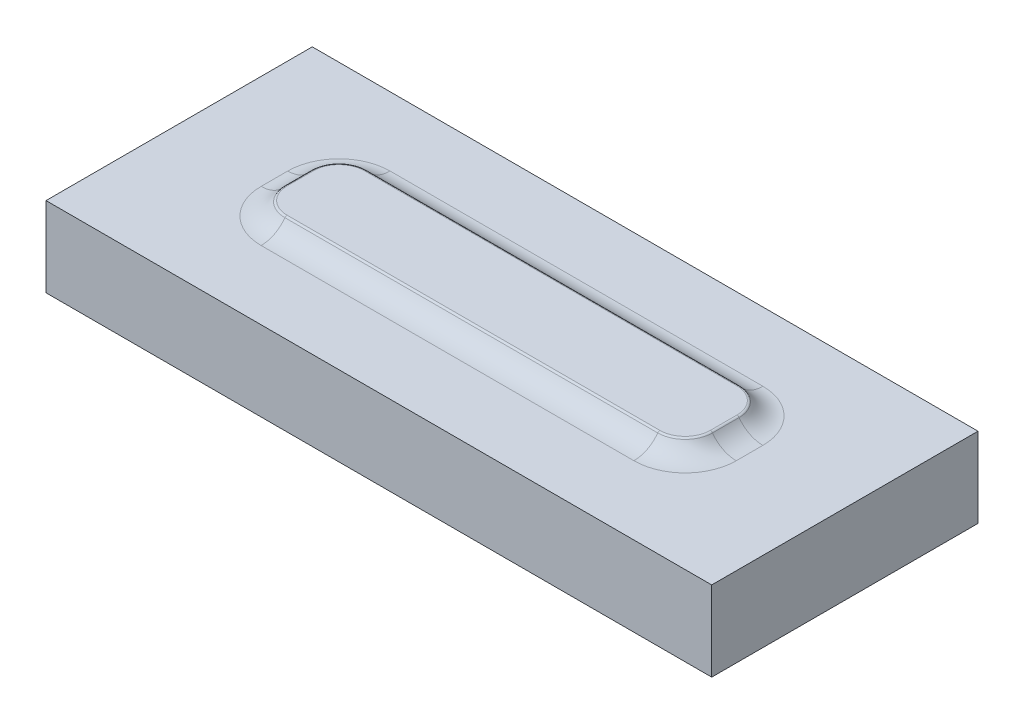
SolidWorks part; units mm, degrees
ref_plane "前视基准面" through (0, 0, 0) normal (0, 0, 1) x (1, 0, 0)
ref_plane "上视基准面" through (0, 0, 0) normal (0, 1, 0) x (1, 0, 0)
ref_plane "右视基准面" through (0, 0, 0) normal (1, 0, 0) x (0, 0, -1)
sketch "草图1" plane through (0, 0, 0) normal (0, 1, 0) x (1, 0, 0)
  line L1 (12.5, 5) -> (-12.5, 5)
  line L2 (12.5, 5) -> (12.5, -5)
  line L3 (12.5, -5) -> (-12.5, -5)
  line L4 (-12.5, 5) -> (-12.5, -5)
  line L5 (12.5, 5) -> (-12.5, -5) construction
  line L6 (12.5, -5) -> (-12.5, 5) construction
  point P0 (0, 0)
  dimension "D1" = 25
  dimension "D2" = 10
extrude "凸台-拉伸1" add sketch "草图1" along normal blind 3
sketch "草图2" plane through (0, 3, 0) normal (0, 1, 0) x (1, 0, 0)
  line L1 (7, 1.5) -> (-7, 1.5)
  line L2 (8, 0.5) -> (8, -0.5)
  line L3 (7, -1.5) -> (-7, -1.5)
  line L4 (-8, 0.5) -> (-8, -0.5)
  line L5 (8, 1.5) -> (-8, -1.5) construction
  line L6 (8, -1.5) -> (-8, 1.5) construction
  arc A0 (-8, -0.5) -> (-7, -1.5) centre (-7, -0.5) ccw
  arc A1 (-7, 1.5) -> (-8, 0.5) centre (-7, 0.5) ccw
  arc A2 (8, -0.5) -> (7, -1.5) centre (7, -0.5) cw
  arc A3 (7, 1.5) -> (8, 0.5) centre (7, 0.5) cw
  point P0 (0, 0)
  dimension "D3" = 1
  dimension "D1" = 16
  dimension "D2" = 3
extrude "凸台-拉伸2" add sketch "草图2" along normal blind 0.5
fillet "圆角1" radius 1.1 8 edges at (-7.7071, 3, 1.2071) (-8, 3, 0) (-7.7071, 3, -1.2071) (0, 3, -1.5) (7.7071, 3, -1.2071) (8, 3, 0) (7.7071, 3, 1.2071) (0, 3, 1.5)
fillet "圆角2" radius 0.1 8 edges at (-7.7071, 3.5, 1.2071) (-8, 3.5, 0) (-7.7071, 3.5, -1.2071) (0, 3.5, -1.5) (7.7071, 3.5, -1.2071) (8, 3.5, 0) (7.7071, 3.5, 1.2071) (0, 3.5, 1.5)
sketch "方向草图" plane through (0, 3, 0) normal (0, 1, 0) x (1, 0, 0)
  line L0 (7, -2.422) -> (-7, -2.422) construction
  line L1 (-8.922, -0.5) -> (-8.922, 0.5) construction
  line L2 (-7, 2.422) -> (7, 2.422) construction
  line L3 (8.922, 0.5) -> (8.922, -0.5) construction
  line L4 (-12.5, 5) -> (-12.5, -5) construction
  line L5 (-12.5, -5) -> (12.5, -5) construction
  line L6 (12.5, -5) -> (12.5, 5) construction
  line L7 (12.5, 5) -> (-12.5, 5) construction
  line L8 (7, -2.422) -> (-7, -2.422)
  line L9 (-8.922, -0.5) -> (-8.922, 0.5)
  line L10 (-7, 2.422) -> (7, 2.422)
  line L11 (8.922, 0.5) -> (8.922, -0.5)
  line L12 (-12.5, 5) -> (-12.5, -5) construction
  line L13 (-12.5, -5) -> (12.5, -5) construction
  line L14 (12.5, -5) -> (12.5, 5) construction
  line L15 (12.5, 5) -> (-12.5, 5) construction
  arc A0 (-8.922, -0.5) -> (-7, -2.422) centre (-7, -0.5) ccw construction
  arc A1 (-7, 2.422) -> (-8.922, 0.5) centre (-7, 0.5) ccw construction
  arc A2 (8.922, 0.5) -> (7, 2.422) centre (7, 0.5) ccw construction
  arc A3 (7, -2.422) -> (8.922, -0.5) centre (7, -0.5) ccw construction
  arc A4 (-8.922, -0.5) -> (-7, -2.422) centre (-7, -0.5) ccw
  arc A5 (-7, 2.422) -> (-8.922, 0.5) centre (-7, 0.5) ccw
  arc A6 (8.922, 0.5) -> (7, 2.422) centre (7, 0.5) ccw
  arc A7 (7, -2.422) -> (8.922, -0.5) centre (7, -0.5) ccw
  point P14 (0, 0)
other "成形工具1"
